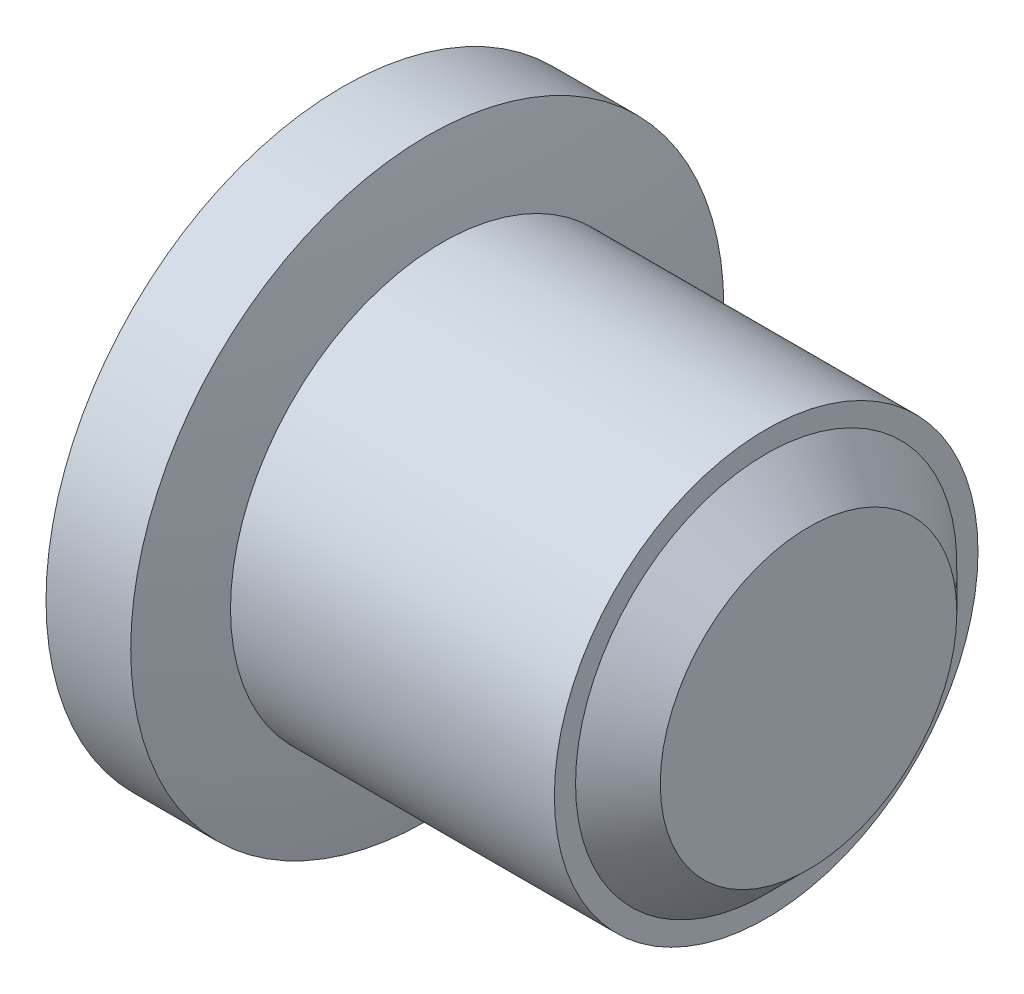
SolidWorks part; units mm, degrees
ref_plane "Front Plane" through (0, 0, 0) normal (0, 0, 1) x (1, 0, 0)
ref_plane "Top Plane" through (0, 0, 0) normal (0, 1, 0) x (1, 0, 0)
ref_plane "Right Plane" through (0, 0, 0) normal (1, 0, 0) x (0, 0, -1)
sketch "Sketch3" plane through (0, 0, 0) normal (0, 0, 1) x (1, 0, 0)
  line L0 (-12.7, 177.8) -> (-63.5, 177.8)
  line L1 (-63.5, 177.8) -> (-63.5, 0)
  line L2 (-63.5, 0) -> (0, 0)
  arc A0 (0, 0) -> (-12.7, 177.8) centre (-607.8669, 45.9345) ccw
  dimension "D1" = 609.6
  dimension "D2" = 177.8
  dimension "D3" = 50.8
  dimension "D4" = 63.5
revolve "Revolve1" add sketch "Sketch3" angle 360 about L2
sketch "Sketch4" plane through (-63.5, 0, 0) normal (-1, 0, 0) x (0, 0, 1)
  circle A0 centre (0, 0) radius 127
  dimension "D1" = 254
extrude "Boss-Extrude1" add sketch "Sketch4" against normal blind 254
sketch "Sketch5" plane through (190.5, 0, 0) normal (1, 0, 0) x (0, 0, -1)
  circle A3 centre (0, 0) radius 114.3
  circle A4 centre (0, 0) radius 114.3
  dimension "D1" = 12.7
extrude "Boss-Extrude2" add sketch "Sketch5" along normal blind 25.4
chamfer "Chamfer1" distance 25.4 angle 45 1 edges at (215.9, 0, -114.3)
